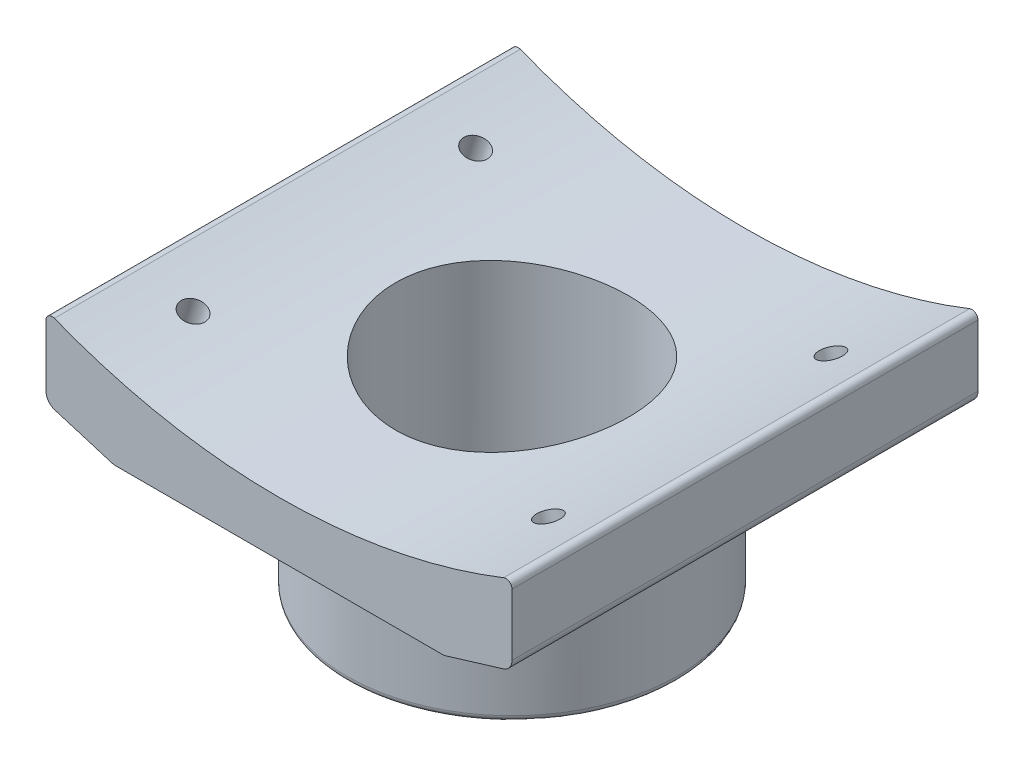
SolidWorks part; units mm, degrees
ref_plane "Plano frontal" through (0, 0, 0) normal (0, 0, 1) x (1, 0, 0)
ref_plane "Plano superior" through (0, 0, 0) normal (0, 1, 0) x (1, 0, 0)
ref_plane "Plano direito" through (0, 0, 0) normal (1, 0, 0) x (0, 0, -1)
ref_plane "Plano1" through (0, 0, -38.1) normal (0, 0, -1) x (-1, 0, 0)
sketch "Esboço1" plane through (0, 0, -38.1) normal (0, 0, -1) x (-1, 0, 0)
  line L0 (-38.1, -3.5741) -> (-38.1, -20)
  line L1 (-38.1, -20) -> (38.1, -20)
  line L2 (38.1, -20) -> (38.1, -3.5741)
  arc A0 (38.1, -3.5741) -> (-38.1, -3.5741) centre (0, 88.8834) cw
extrude "Ressalto-extrusão1" add sketch "Esboço1" against normal blind 76.2
ref_plane "Plano2" through (0, 0, 0) normal (0, 0, -1) x (-1, 0, 0)
sketch "Esboço2" plane through (0, 0, 0) normal (0, 0, -1) x (-1, 0, 0)
  line L0 (-27, -43) -> (0, -43)
  line L1 (0, -43) -> (0, -20)
  line L2 (0, -20) -> (-27, -20)
  line L3 (-27, -20) -> (-27, -43)
  line L4 (0, -43) -> (0, -20) construction
  line L5 (-38.1, -20) -> (38.1, -20) construction
  dimension "D1" = 23
  dimension "D2" = 27
revolve "Revolução1" add sketch "Esboço2" angle 360 about L4 reverse direction yes
hole_wizard "Furo com folga de M361" positions "Esboço4" profile "Esboço3" hole size "M36" standard "Ansi Metric"
sketch "Esboço4" plane through (0, -43, 0) normal (0, -1, 0) x (-1, 0, 0)
  point P0 (0, 0)
sketch "Esboço3" plane through (0, -43, 0) normal (1, 0, 0) x (0, 0, -1)
  line L0 (0, 0) -> (0, 39.4259)
  line L1 (0, 39.4259) -> (19.05, 39.4259)
  line L2 (19.05, 39.4259) -> (19.05, 0)
  line L5 (19.05, 0) -> (0, 0)
  line L11 (0, -6.35) -> (0, 107.95) construction
  dimension "Thru Hole Dia." = 38.1
  dimension "Thru Hole Depth" = 39.4259
fillet "Filete1" radius 1 3 edges at (-27, -43, 0) (38.1, -3.5741, 0) (-38.1, -3.5741, 0)
sketch "Esboço5" plane through (0, 0, -38.1) normal (0, 0, -1) x (-1, 0, 0)
  line L0 (7.6057, -13.3155) -> (50.5032, -0.29) construction
  line L1 (27, -20) -> (38.1, -16.6296)
  line L2 (-38.1, -20) -> (38.1, -20) construction
  line L3 (38.1, -20) -> (38.1, -5.0559) construction
  line L4 (32.55, -18.3148) -> (29.0544, -6.8027) construction
  line L5 (38.1, -16.6296) -> (38.1, -20)
  line L6 (38.1, -20) -> (27, -20)
  line L7 (0, 0) -> (0, -43) construction
  line L8 (-26, -43) -> (26, -43) construction
  line L9 (-38.1, -20) -> (-27, -20)
  line L10 (-38.1, -16.6296) -> (-38.1, -20)
  line L11 (-27, -20) -> (-38.1, -16.6296)
  arc A0 (-36.7327, -4.1258) -> (36.7327, -4.1258) centre (0, 88.8834) ccw construction
  point P9 (29.0544, -6.8027)
  point P25 (38.1, -17.7233)
  point P26 (38.1, -20)
extrude "Corte-extrusão1" cut sketch "Esboço5" against normal through all
sketch "Esboço6" plane through (-7.8395, -25.818, 0) normal (-0.2905, -0.9569, 0) x (0.9569, -0.2905, 0)
  line L0 (-25.8246, 38.1) -> (-25.8246, 23.1) construction
  line L1 (-31.6248, 38.1) -> (-20.0244, 38.1) construction
  line L2 (-25.8246, 23.1) -> (-25.8246, -23.1) construction
  line L3 (-25.8246, -23.1) -> (-25.8246, -38.1) construction
  line L4 (31.6461, -38.1) -> (-20.0244, -38.1) construction
  circle A0 centre (-25.8246, 23.1) radius 2
  circle A1 centre (-25.8246, -23.1) radius 2
  point P8 (0, 0)
  dimension "D2" = 4
  dimension "D1" = 15
extrude "Corte-extrusão2" cut sketch "Esboço6" against normal through all
mirror "Espelhar1" about plane through (0, 0, 0) normal (1, 0, 0) of "Corte-extrusão2"
fillet "Filete2" radius 2 6 edges at (27, -20, 19.05) (-27, -20, 19.05) (38.1, -16.6296, 0) (27, -20, -19.05) (-27, -20, -19.05) (-38.1, -16.6296, 0)
fillet "Filete3" radius 0.5 1 edges at (0, -43, -19.05)
